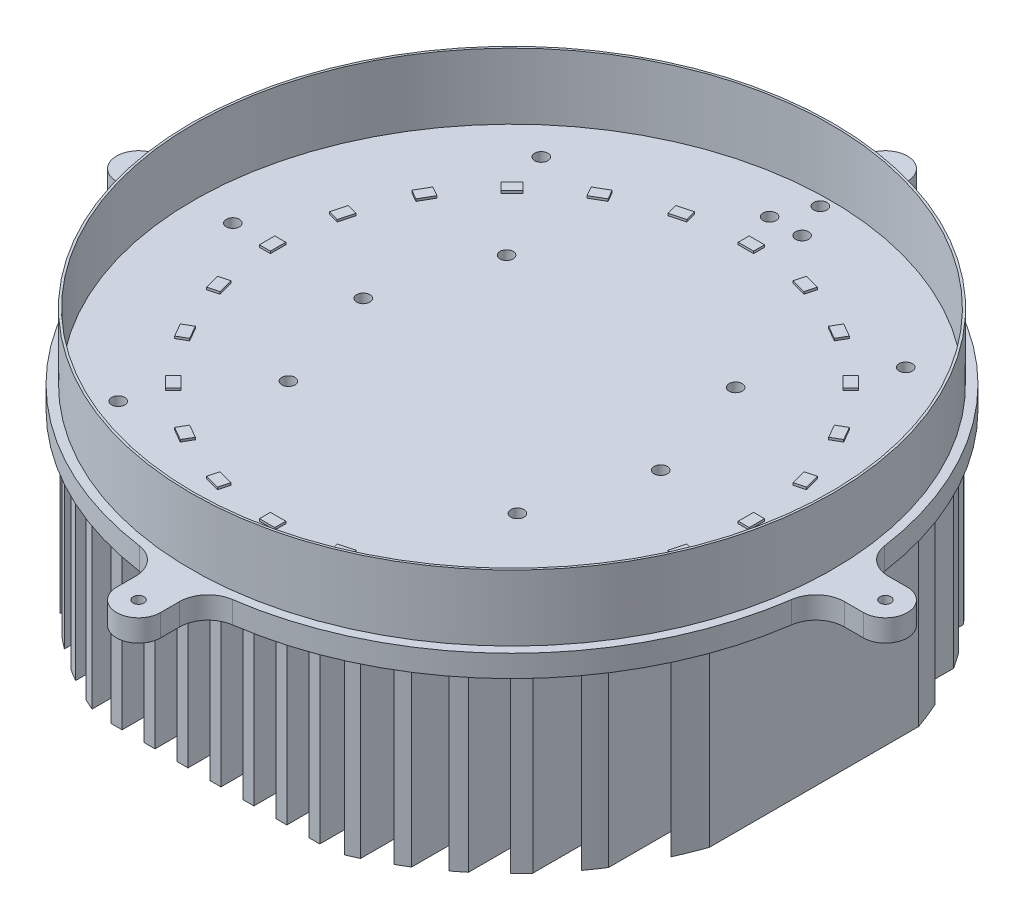
SolidWorks part; units mm, degrees
ref_plane "Front Plane" through (0, 0, 0) normal (0, 0, 1) x (1, 0, 0)
ref_plane "Top Plane" through (0, 0, 0) normal (0, 1, 0) x (1, 0, 0)
ref_plane "Right Plane" through (0, 0, 0) normal (1, 0, 0) x (0, 0, -1)
sketch "Sketch2" plane through (0, 0, 0) normal (0, 1, 0) x (1, 0, 0)
  line L0 (0, 0) -> (0, -224.3017) construction
  line L1 (0, 0) -> (0, 200) construction
  line L2 (0, 0) -> (207.2583, 0) construction
  line L3 (0, 0) -> (-200, 0) construction
  circle A0 centre (0, 0) radius 146
  circle A1 centre (0, 0) radius 145
  point P36 (0, 0)
  dimension "D1" = 290
  dimension "D2" = 292
extrude "Boss-Extrude2" add sketch "Sketch2" along normal blind 30 contours A1 | A0
sketch "Sketch3" plane through (0, 0, 0) normal (0, 1, 0) x (1, 0, 0)
  line L0 (0, 0) -> (211.9111, 0) construction
  line L1 (0, 0) -> (-205.2426, 0) construction
  line L2 (0, 0) -> (0, 170) construction
  line L3 (0, 0) -> (0, -200) construction
  line L4 (161.3691, 10) -> (170, 10)
  line L5 (161.3691, -10) -> (170, -10)
  line L6 (-10, 161.3691) -> (-10, 170)
  line L7 (10, 161.3691) -> (10, 170)
  line L8 (10, -161.3691) -> (10, -170)
  line L9 (-10, -161.3691) -> (-10, -170)
  line L10 (-161.3691, -10) -> (-170, -10)
  line L11 (-161.3691, 10) -> (-170, 10)
  arc A0 (-21.1656, 148.4992) -> (-148.4992, 21.1656) centre (0, 0) ccw
  circle A1 centre (0, 170) radius 2.5
  arc A2 (-10, 170) -> (10, 170) centre (0, 170) cw
  arc A3 (10, 161.3691) -> (21.1656, 148.4992) centre (23, 161.3691) ccw
  arc A4 (-10, 161.3691) -> (-21.1656, 148.4992) centre (-23, 161.3691) cw
  arc A5 (170, 10) -> (170, -10) centre (170, 0) cw
  arc A6 (161.3691, 10) -> (148.4992, 21.1656) centre (161.3691, 23) cw
  circle A7 centre (170, 0) radius 2.5
  arc A8 (161.3691, -10) -> (148.4992, -21.1656) centre (161.3691, -23) ccw
  arc A9 (10, -170) -> (-10, -170) centre (0, -170) cw
  arc A10 (10, -161.3691) -> (21.1656, -148.4992) centre (23, -161.3691) cw
  circle A11 centre (0, -170) radius 2.5
  arc A12 (-10, -161.3691) -> (-21.1656, -148.4992) centre (-23, -161.3691) ccw
  arc A13 (-170, -10) -> (-170, 10) centre (-170, 0) cw
  arc A14 (-161.3691, -10) -> (-148.4992, -21.1656) centre (-161.3691, -23) cw
  circle A15 centre (-170, 0) radius 2.5
  arc A16 (-161.3691, 10) -> (-148.4992, 21.1656) centre (-161.3691, 23) ccw
  arc A17 (-148.4992, -21.1656) -> (-21.1656, -148.4992) centre (0, 0) ccw
  arc A18 (148.4992, 21.1656) -> (21.1656, 148.4992) centre (0, 0) ccw
  arc A19 (21.1656, -148.4992) -> (148.4992, -21.1656) centre (0, 0) ccw
  point P53 (0, 0)
  dimension "D1" = 300
  dimension "D4" = 5
  dimension "D2" = 4
extrude "Boss-Extrude4" add sketch "Sketch3" against normal blind 10
sketch "Sketch4" plane through (0, -10, 0) normal (0, -1, 0) x (1, 0, 0)
  line L0 (0, 0) -> (0, -192.7937) construction
  line L1 (0, 0) -> (0, 216.5128) construction
  line L2 (0, 0) -> (-235.9747, 0) construction
  line L3 (0, 0) -> (242.3846, 0) construction
  line L4 (2.5, -135) -> (-2.5, -135)
  line L5 (2.5, 135) -> (-2.5, 135)
  line L6 (-2.5, -135) -> (-2.5, 135)
  line L7 (2.5, -135) -> (2.5, 135)
  line L8 (12.5, -135) -> (12.5, 135)
  line L9 (17.5, -135) -> (12.5, -135)
  line L10 (17.5, -135) -> (17.5, 135)
  line L11 (17.5, 135) -> (12.5, 135)
  line L12 (27.5, -135) -> (27.5, 135)
  line L13 (32.5, -135) -> (27.5, -135)
  line L14 (32.5, -135) -> (32.5, 135)
  line L15 (32.5, 135) -> (27.5, 135)
  line L16 (42.5, -135) -> (42.5, 135)
  line L17 (47.5, -135) -> (42.5, -135)
  line L18 (47.5, -135) -> (47.5, 135)
  line L19 (47.5, 135) -> (42.5, 135)
  line L20 (57.5, -133.6563) -> (57.5, 133.6563)
  line L22 (62.5, -131.3925) -> (62.5, 131.3925)
  line L24 (72.5, -126.1507) -> (72.5, 126.1507)
  line L26 (77.5, -123.1422) -> (77.5, 123.1422)
  line L28 (87.5, -116.2497) -> (87.5, 116.2497)
  line L30 (92.5, -112.3121) -> (92.5, 112.3121)
  line L32 (102.5, -103.2666) -> (102.5, 103.2666)
  line L34 (107.5, -98.051) -> (107.5, 98.051)
  line L36 (117.5, -85.8138) -> (117.5, 85.8138)
  line L38 (122.5, -78.5111) -> (122.5, 78.5111)
  line L40 (132.5, -60.1166) -> (132.5, 60.1166)
  line L42 (137.5, -47.5815) -> (137.5, 47.5815)
  line L44 (-12.5, -135) -> (-17.5, -135)
  line L45 (-12.5, -135) -> (-12.5, 135)
  line L46 (-17.5, -135) -> (-17.5, 135)
  line L47 (-12.5, 135) -> (-17.5, 135)
  line L48 (-27.5, -135) -> (-32.5, -135)
  line L49 (-27.5, -135) -> (-27.5, 135)
  line L50 (-32.5, -135) -> (-32.5, 135)
  line L51 (-27.5, 135) -> (-32.5, 135)
  line L52 (-42.5, -135) -> (-47.5, -135)
  line L53 (-42.5, -135) -> (-42.5, 135)
  line L54 (-47.5, -135) -> (-47.5, 135)
  line L55 (-42.5, 135) -> (-47.5, 135)
  line L57 (-57.5, -133.6563) -> (-57.5, 133.6563)
  line L58 (-62.5, -131.3925) -> (-62.5, 131.3925)
  line L61 (-72.5, -126.1507) -> (-72.5, 126.1507)
  line L62 (-77.5, -123.1422) -> (-77.5, 123.1422)
  line L65 (-87.5, -116.2497) -> (-87.5, 116.2497)
  line L66 (-92.5, -112.3121) -> (-92.5, 112.3121)
  line L69 (-102.5, -103.2666) -> (-102.5, 103.2666)
  line L70 (-107.5, -98.051) -> (-107.5, 98.051)
  line L73 (-117.5, -85.8138) -> (-117.5, 85.8138)
  line L74 (-122.5, -78.5111) -> (-122.5, 78.5111)
  line L77 (-132.5, -60.1166) -> (-132.5, 60.1166)
  line L78 (-137.5, -47.5815) -> (-137.5, 47.5815)
  line L80 (2.5, -135) -> (-12.5, -135) construction
  line L81 (62.5, 135) -> (57.5, 135) [skipped]
  line L82 (77.5, 135) -> (72.5, 135) [skipped]
  line L83 (92.5, 135) -> (87.5, 135) [skipped]
  line L84 (107.5, 135) -> (102.5, 135) [skipped]
  line L85 (137.5, 135) -> (132.5, 135) [skipped]
  line L86 (122.5, 135) -> (117.5, 135) [skipped]
  line L87 (-57.5, 135) -> (-62.5, 135) [skipped]
  line L88 (-72.5, 135) -> (-77.5, 135) [skipped]
  line L89 (-87.5, 135) -> (-92.5, 135) [skipped]
  line L90 (-102.5, 135) -> (-107.5, 135) [skipped]
  line L91 (-117.5, 135) -> (-122.5, 135) [skipped]
  line L92 (-132.5, 135) -> (-137.5, 135) [skipped]
  line L93 (-57.5, -135) -> (-62.5, -135) [skipped]
  line L94 (62.5, -135) -> (57.5, -135) [skipped]
  line L95 (77.5, -135) -> (72.5, -135) [skipped]
  line L96 (137.5, -135) -> (132.5, -135) [skipped]
  line L97 (122.5, -135) -> (117.5, -135) [skipped]
  line L98 (107.5, -135) -> (102.5, -135) [skipped]
  line L99 (92.5, -135) -> (87.5, -135) [skipped]
  line L100 (-132.5, -135) -> (-137.5, -135) [skipped]
  line L101 (-117.5, -135) -> (-122.5, -135) [skipped]
  line L102 (-102.5, -135) -> (-107.5, -135) [skipped]
  line L103 (-87.5, -135) -> (-92.5, -135) [skipped]
  line L104 (-72.5, -135) -> (-77.5, -135) [skipped]
  arc A2 (132.5, -60.1166) -> (137.5, -47.5815) centre (0, 0) ccw
  arc A3 (117.5, -85.8138) -> (122.5, -78.5111) centre (0, 0) ccw
  arc A4 (102.5, -103.2666) -> (107.5, -98.051) centre (0, 0) ccw
  arc A5 (87.5, -116.2497) -> (92.5, -112.3121) centre (0, 0) ccw
  arc A6 (72.5, -126.1507) -> (77.5, -123.1422) centre (0, 0) ccw
  arc A7 (57.5, -133.6563) -> (62.5, -131.3925) centre (0, 0) ccw
  arc A8 (-77.5, -123.1422) -> (-72.5, -126.1507) centre (0, 0) ccw
  arc A9 (-62.5, -131.3925) -> (-57.5, -133.6563) centre (0, 0) ccw
  arc A10 (-92.5, -112.3121) -> (-87.5, -116.2497) centre (0, 0) ccw
  arc A11 (-107.5, -98.051) -> (-102.5, -103.2666) centre (0, 0) ccw
  arc A12 (-122.5, -78.5111) -> (-117.5, -85.8138) centre (0, 0) ccw
  arc A13 (-137.5, -47.5815) -> (-132.5, -60.1166) centre (0, 0) ccw
  arc A14 (137.5, 47.5815) -> (132.5, 60.1166) centre (0, 0) ccw
  arc A15 (122.5, 78.5111) -> (117.5, 85.8138) centre (0, 0) ccw
  arc A16 (107.5, 98.051) -> (102.5, 103.2666) centre (0, 0) ccw
  arc A17 (92.5, 112.3121) -> (87.5, 116.2497) centre (0, 0) ccw
  arc A18 (77.5, 123.1422) -> (72.5, 126.1507) centre (0, 0) ccw
  arc A19 (62.5, 131.3925) -> (57.5, 133.6563) centre (0, 0) ccw
  arc A20 (-57.5, 133.6563) -> (-62.5, 131.3925) centre (0, 0) ccw
  arc A21 (-72.5, 126.1507) -> (-77.5, 123.1422) centre (0, 0) ccw
  arc A22 (-87.5, 116.2497) -> (-92.5, 112.3121) centre (0, 0) ccw
  arc A23 (-102.5, 103.2666) -> (-107.5, 98.051) centre (0, 0) ccw
  arc A24 (-117.5, 85.8138) -> (-122.5, 78.5111) centre (0, 0) ccw
  arc A25 (-132.5, 60.1166) -> (-137.5, 47.5815) centre (0, 0) ccw
  point P24 (-53.3541, 55.5795)
  dimension "D5" = 291
  dimension "D1" = 135
  dimension "D2" = 2.5
  dimension "D4" = 15
  dimension "D3" = 10
extrude "Boss-Extrude5" add sketch "Sketch4" along normal blind 80
sketch "Sketch5" plane through (0, 0, 0) normal (0, 1, 0) x (1, 0, 0)
  line L0 (0, 0) -> (233.0388, 0) construction
  line L1 (0, 0) -> (-266.1331, 0) construction
  line L2 (0, 0) -> (0, 192.8201) construction
  line L3 (0, 0) -> (0, -200.634) construction
  line L4 (0, 111.4786) -> (3.5, 111.4786)
  line L5 (0, 111.4786) -> (-3.5, 111.4786)
  line L6 (3.5, 106.4786) -> (3.5, 111.4786)
  line L7 (-3.5, 106.4786) -> (-3.5, 111.4786)
  line L8 (0, 106.4786) -> (3.5, 106.4786)
  line L9 (0, 106.4786) -> (-3.5, 106.4786)
  line L10 (24.1779, 103.7563) -> (25.472, 108.5859)
  line L11 (28.8528, 107.68) -> (25.472, 108.5859)
  line L12 (28.8528, 107.68) -> (32.2335, 106.7742)
  line L13 (30.9394, 101.9445) -> (32.2335, 106.7742)
  line L14 (27.5587, 102.8504) -> (30.9394, 101.9445)
  line L15 (27.5587, 102.8504) -> (24.1779, 103.7563)
  line L16 (50.2082, 93.9631) -> (52.7082, 98.2933)
  line L17 (55.7393, 96.5433) -> (52.7082, 98.2933)
  line L18 (55.7393, 96.5433) -> (58.7704, 94.7933)
  line L19 (56.2704, 90.4631) -> (58.7704, 94.7933)
  line L20 (53.2393, 92.2131) -> (56.2704, 90.4631)
  line L21 (53.2393, 92.2131) -> (50.2082, 93.9631)
  line L22 (72.8168, 77.7666) -> (76.3524, 81.3021)
  line L23 (78.8273, 78.8273) -> (76.3524, 81.3021)
  line L24 (78.8273, 78.8273) -> (81.3021, 76.3524)
  line L25 (77.7666, 72.8168) -> (81.3021, 76.3524)
  line L26 (75.2917, 75.2917) -> (77.7666, 72.8168)
  line L27 (75.2917, 75.2917) -> (72.8168, 77.7666)
  line L28 (90.4631, 56.2704) -> (94.7933, 58.7704)
  line L29 (96.5433, 55.7393) -> (94.7933, 58.7704)
  line L30 (96.5433, 55.7393) -> (98.2933, 52.7082)
  line L31 (93.9631, 50.2082) -> (98.2933, 52.7082)
  line L32 (92.2131, 53.2393) -> (93.9631, 50.2082)
  line L33 (92.2131, 53.2393) -> (90.4631, 56.2704)
  line L34 (101.9445, 30.9394) -> (106.7742, 32.2335)
  line L35 (107.68, 28.8528) -> (106.7742, 32.2335)
  line L36 (107.68, 28.8528) -> (108.5859, 25.472)
  line L37 (103.7563, 24.1779) -> (108.5859, 25.472)
  line L38 (102.8504, 27.5587) -> (103.7563, 24.1779)
  line L39 (102.8504, 27.5587) -> (101.9445, 30.9394)
  line L40 (106.4786, 3.5) -> (111.4786, 3.5)
  line L41 (111.4786, 0) -> (111.4786, 3.5)
  line L42 (111.4786, 0) -> (111.4786, -3.5)
  line L43 (106.4786, -3.5) -> (111.4786, -3.5)
  line L44 (106.4786, 0) -> (106.4786, -3.5)
  line L45 (106.4786, 0) -> (106.4786, 3.5)
  line L46 (103.7563, -24.1779) -> (108.5859, -25.472)
  line L47 (107.68, -28.8528) -> (108.5859, -25.472)
  line L48 (107.68, -28.8528) -> (106.7742, -32.2335)
  line L49 (101.9445, -30.9394) -> (106.7742, -32.2335)
  line L50 (102.8504, -27.5587) -> (101.9445, -30.9394)
  line L51 (102.8504, -27.5587) -> (103.7563, -24.1779)
  line L52 (93.9631, -50.2082) -> (98.2933, -52.7082)
  line L53 (96.5433, -55.7393) -> (98.2933, -52.7082)
  line L54 (96.5433, -55.7393) -> (94.7933, -58.7704)
  line L55 (90.4631, -56.2704) -> (94.7933, -58.7704)
  line L56 (92.2131, -53.2393) -> (90.4631, -56.2704)
  line L57 (92.2131, -53.2393) -> (93.9631, -50.2082)
  line L58 (77.7666, -72.8168) -> (81.3021, -76.3524)
  line L59 (78.8273, -78.8273) -> (81.3021, -76.3524)
  line L60 (78.8273, -78.8273) -> (76.3524, -81.3021)
  line L61 (72.8168, -77.7666) -> (76.3524, -81.3021)
  line L62 (75.2917, -75.2917) -> (72.8168, -77.7666)
  line L63 (75.2917, -75.2917) -> (77.7666, -72.8168)
  line L64 (56.2704, -90.4631) -> (58.7704, -94.7933)
  line L65 (55.7393, -96.5433) -> (58.7704, -94.7933)
  line L66 (55.7393, -96.5433) -> (52.7082, -98.2933)
  line L67 (50.2082, -93.9631) -> (52.7082, -98.2933)
  line L68 (53.2393, -92.2131) -> (50.2082, -93.9631)
  line L69 (53.2393, -92.2131) -> (56.2704, -90.4631)
  line L70 (30.9394, -101.9445) -> (32.2335, -106.7742)
  line L71 (28.8528, -107.68) -> (32.2335, -106.7742)
  line L72 (28.8528, -107.68) -> (25.472, -108.5859)
  line L73 (24.1779, -103.7563) -> (25.472, -108.5859)
  line L74 (27.5587, -102.8504) -> (24.1779, -103.7563)
  line L75 (27.5587, -102.8504) -> (30.9394, -101.9445)
  line L76 (3.5, -106.4786) -> (3.5, -111.4786)
  line L77 (0, -111.4786) -> (3.5, -111.4786)
  line L78 (0, -111.4786) -> (-3.5, -111.4786)
  line L79 (-3.5, -106.4786) -> (-3.5, -111.4786)
  line L80 (0, -106.4786) -> (-3.5, -106.4786)
  line L81 (0, -106.4786) -> (3.5, -106.4786)
  line L82 (-24.1779, -103.7563) -> (-25.472, -108.5859)
  line L83 (-28.8528, -107.68) -> (-25.472, -108.5859)
  line L84 (-28.8528, -107.68) -> (-32.2335, -106.7742)
  line L85 (-30.9394, -101.9445) -> (-32.2335, -106.7742)
  line L86 (-27.5587, -102.8504) -> (-30.9394, -101.9445)
  line L87 (-27.5587, -102.8504) -> (-24.1779, -103.7563)
  line L88 (-50.2082, -93.9631) -> (-52.7082, -98.2933)
  line L89 (-55.7393, -96.5433) -> (-52.7082, -98.2933)
  line L90 (-55.7393, -96.5433) -> (-58.7704, -94.7933)
  line L91 (-56.2704, -90.4631) -> (-58.7704, -94.7933)
  line L92 (-53.2393, -92.2131) -> (-56.2704, -90.4631)
  line L93 (-53.2393, -92.2131) -> (-50.2082, -93.9631)
  line L94 (-72.8168, -77.7666) -> (-76.3524, -81.3021)
  line L95 (-78.8273, -78.8273) -> (-76.3524, -81.3021)
  line L96 (-78.8273, -78.8273) -> (-81.3021, -76.3524)
  line L97 (-77.7666, -72.8168) -> (-81.3021, -76.3524)
  line L98 (-75.2917, -75.2917) -> (-77.7666, -72.8168)
  line L99 (-75.2917, -75.2917) -> (-72.8168, -77.7666)
  line L100 (-90.4631, -56.2704) -> (-94.7933, -58.7704)
  line L101 (-96.5433, -55.7393) -> (-94.7933, -58.7704)
  line L102 (-96.5433, -55.7393) -> (-98.2933, -52.7082)
  line L103 (-93.9631, -50.2082) -> (-98.2933, -52.7082)
  line L104 (-92.2131, -53.2393) -> (-93.9631, -50.2082)
  line L105 (-92.2131, -53.2393) -> (-90.4631, -56.2704)
  line L106 (-101.9445, -30.9394) -> (-106.7742, -32.2335)
  line L107 (-107.68, -28.8528) -> (-106.7742, -32.2335)
  line L108 (-107.68, -28.8528) -> (-108.5859, -25.472)
  line L109 (-103.7563, -24.1779) -> (-108.5859, -25.472)
  line L110 (-102.8504, -27.5587) -> (-103.7563, -24.1779)
  line L111 (-102.8504, -27.5587) -> (-101.9445, -30.9394)
  line L112 (-106.4786, -3.5) -> (-111.4786, -3.5)
  line L113 (-111.4786, 0) -> (-111.4786, -3.5)
  line L114 (-111.4786, 0) -> (-111.4786, 3.5)
  line L115 (-106.4786, 3.5) -> (-111.4786, 3.5)
  line L116 (-106.4786, 0) -> (-106.4786, 3.5)
  line L117 (-106.4786, 0) -> (-106.4786, -3.5)
  line L118 (-103.7563, 24.1779) -> (-108.5859, 25.472)
  line L119 (-107.68, 28.8528) -> (-108.5859, 25.472)
  line L120 (-107.68, 28.8528) -> (-106.7742, 32.2335)
  line L121 (-101.9445, 30.9394) -> (-106.7742, 32.2335)
  line L122 (-102.8504, 27.5587) -> (-101.9445, 30.9394)
  line L123 (-102.8504, 27.5587) -> (-103.7563, 24.1779)
  line L124 (-93.9631, 50.2082) -> (-98.2933, 52.7082)
  line L125 (-96.5433, 55.7393) -> (-98.2933, 52.7082)
  line L126 (-96.5433, 55.7393) -> (-94.7933, 58.7704)
  line L127 (-90.4631, 56.2704) -> (-94.7933, 58.7704)
  line L128 (-92.2131, 53.2393) -> (-90.4631, 56.2704)
  line L129 (-92.2131, 53.2393) -> (-93.9631, 50.2082)
  line L130 (-77.7666, 72.8168) -> (-81.3021, 76.3524)
  line L131 (-78.8273, 78.8273) -> (-81.3021, 76.3524)
  line L132 (-78.8273, 78.8273) -> (-76.3524, 81.3021)
  line L133 (-72.8168, 77.7666) -> (-76.3524, 81.3021)
  line L134 (-75.2917, 75.2917) -> (-72.8168, 77.7666)
  line L135 (-75.2917, 75.2917) -> (-77.7666, 72.8168)
  line L136 (-56.2704, 90.4631) -> (-58.7704, 94.7933)
  line L137 (-55.7393, 96.5433) -> (-58.7704, 94.7933)
  line L138 (-55.7393, 96.5433) -> (-52.7082, 98.2933)
  line L139 (-50.2082, 93.9631) -> (-52.7082, 98.2933)
  line L140 (-53.2393, 92.2131) -> (-50.2082, 93.9631)
  line L141 (-53.2393, 92.2131) -> (-56.2704, 90.4631)
  line L142 (-30.9394, 101.9445) -> (-32.2335, 106.7742)
  line L143 (-28.8528, 107.68) -> (-32.2335, 106.7742)
  line L144 (-28.8528, 107.68) -> (-25.472, 108.5859)
  line L145 (-24.1779, 103.7563) -> (-25.472, 108.5859)
  line L146 (-27.5587, 102.8504) -> (-24.1779, 103.7563)
  line L147 (-27.5587, 102.8504) -> (-30.9394, 101.9445)
  point P33 (0, 0)
  dimension "D1" = 3.5
  dimension "D2" = 5
  dimension "D3" = 24
extrude "Boss-Extrude6" add sketch "Sketch5" along normal blind 1
sketch "Sketch7" plane through (0, 0, 0) normal (0, 1, 0) x (1, 0, 0)
  line L0 (0, 0) -> (0, 199.2983) construction
  line L1 (180, 0) -> (-209.1437, 0) construction
  line L2 (0, 0) -> (0, -219.846) construction
  arc A0 (170, -10) -> (170, 10) centre (170, 0) ccw construction
  circle A1 centre (-127.0882, 0) radius 3
  circle A2 centre (0, 140.3779) radius 3
  circle A3 centre (0, -140.3779) radius 3
  circle A4 centre (127.0882, 0) radius 3
  circle A5 centre (-67.7124, 0) radius 3
  circle A6 centre (-52.1309, 49.6625) radius 3
  circle A7 centre (52.1309, 49.6625) radius 3
  circle A8 centre (52.1309, -49.6625) radius 3
  circle A9 centre (-52.1309, -49.6625) radius 3
  circle A10 centre (67.7124, 0) radius 3
  circle A11 centre (-82.9543, 96.2809) radius 3
  circle A12 centre (82.9543, 96.2809) radius 3
  circle A13 centre (82.9543, -96.2809) radius 3
  circle A14 centre (-82.9543, -96.2809) radius 3
  circle A15 centre (7.3999, -124.6624) radius 3
  circle A16 centre (-7.3999, -124.6624) radius 3
  circle A17 centre (7.3999, 124.6624) radius 3
  circle A18 centre (-7.3999, 124.6624) radius 3
  dimension "D2" = 6
extrude "Cut-Extrude1" cut sketch "Sketch7" against normal blind 10
